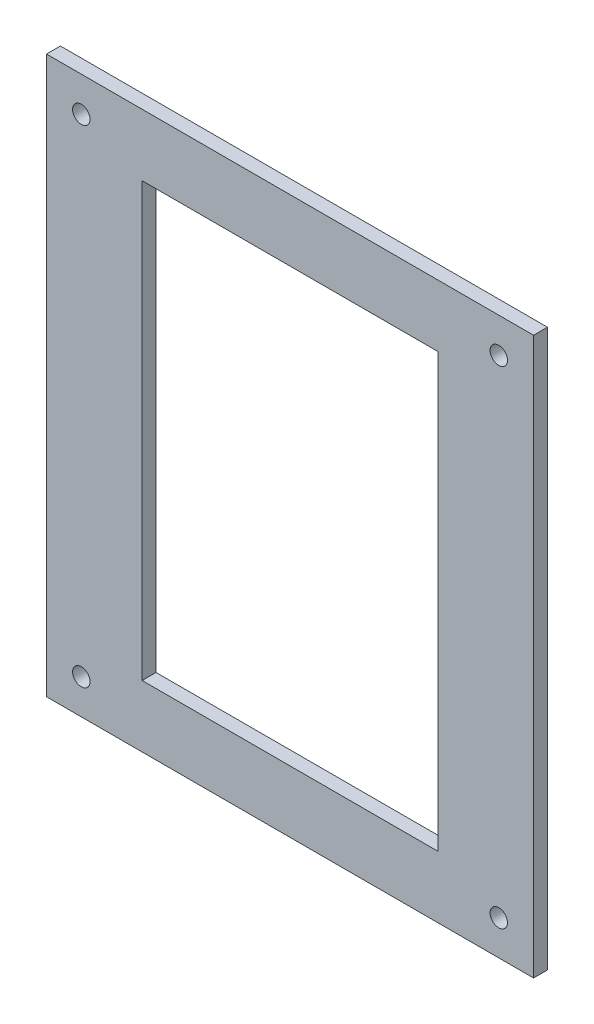
SolidWorks part; units mm, degrees
ref_plane "Front Plane" through (0, 0, 0) normal (0, 0, 1) x (1, 0, 0)
ref_plane "Top Plane" through (0, 0, 0) normal (0, 1, 0) x (1, 0, 0)
ref_plane "Right Plane" through (0, 0, 0) normal (1, 0, 0) x (0, 0, -1)
sketch "Sketch1" plane through (0, 0, 0) normal (0, 0, 1) x (1, 0, 0)
  line L0 (6.35, -6.35) -> (82.55, -6.35) construction
  line L1 (0, 0) -> (88.9, 0)
  line L2 (0, 0) -> (0, -101.6)
  line L3 (0, -101.6) -> (88.9, -101.6)
  line L4 (88.9, 0) -> (88.9, -101.6)
  line L5 (17.45, -11.3) -> (71.45, -11.3)
  line L6 (17.45, -11.3) -> (17.45, -90.3)
  line L7 (17.45, -90.3) -> (71.45, -90.3)
  line L8 (71.45, -11.3) -> (71.45, -90.3)
  line L9 (82.55, -6.35) -> (82.55, -95.25) construction
  line L10 (82.55, -95.25) -> (6.35, -95.25) construction
  line L11 (6.35, -95.25) -> (6.35, -6.35) construction
  line L13 (14.45, -8.3) -> (74.45, -8.3) construction
  line L14 (14.45, -8.3) -> (14.45, -93.3) construction
  line L15 (14.45, -93.3) -> (74.45, -93.3) construction
  line L16 (74.45, -8.3) -> (74.45, -93.3) construction
  circle A0 centre (6.35, -6.35) radius 1.59
  circle A1 centre (82.55, -6.35) radius 1.59
  circle A2 centre (82.55, -95.25) radius 1.59
  circle A3 centre (6.35, -95.25) radius 1.59
  point P17 (44.45, -8.3)
  point P18 (74.45, -50.8)
  point P19 (44.45, 0)
  point P20 (44.45, -6.35)
  point P21 (82.55, -50.8)
  point P22 (88.9, -50.8)
  point P24 (44.45, -11.3)
  point P25 (71.45, -50.8)
  dimension "D3" = 3.18
  dimension "D4" = 76.2
  dimension "D5" = 88.9
  dimension "D6" = 101.6
  dimension "D7" = 85
  dimension "D8" = 60
  dimension "D1" = 3
  dimension "D9" = 79
  dimension "D2" = 3
  dimension "D10" = 54
  dimension "D11" = 88.9
extrude "Boss-Extrude1" add sketch "Sketch1" along normal blind 2.54
equation "\"D4@Sketch1\"=3.0*25.4"
equation "\"D6@Sketch1\"=4in"
equation "\"D11@Sketch1\"=3.5*25.4"
